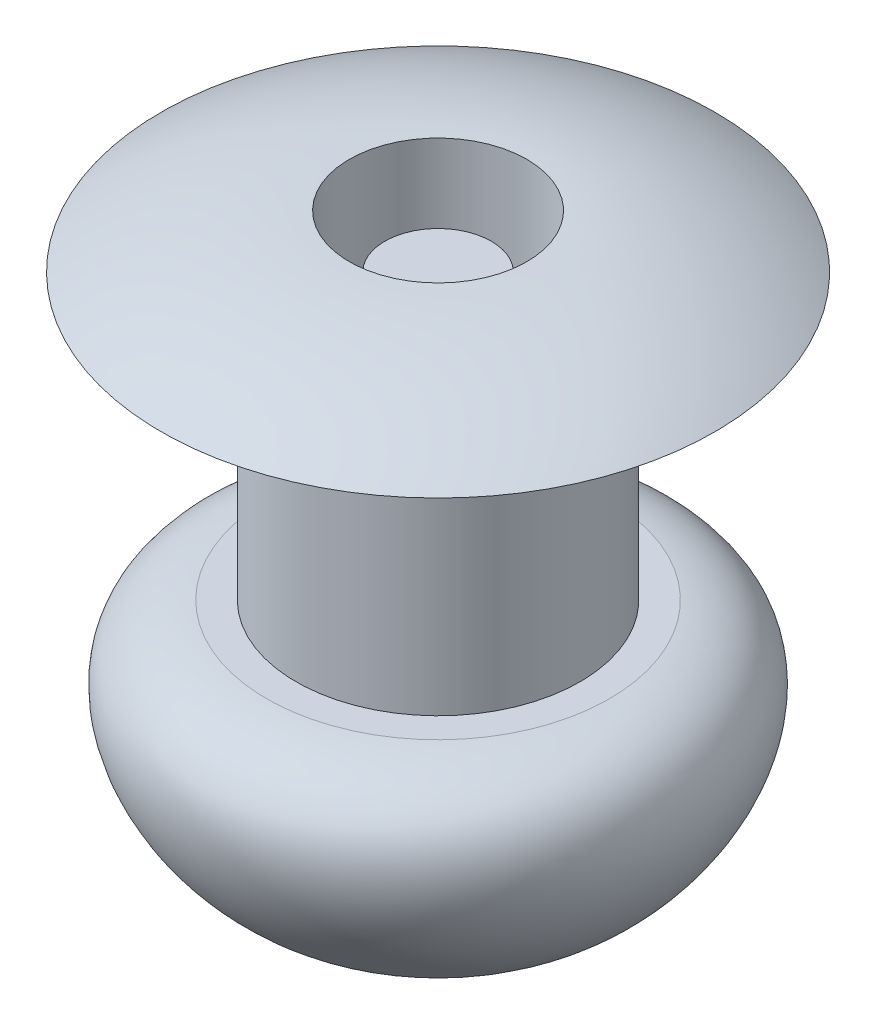
SolidWorks part; units mm, degrees
material "AISI 316 Stal nierdzewna odprężona (SS)"
ref_plane "Płaszczyzna przednia" through (0, 0, 0) normal (0, 0, 1) x (1, 0, 0)
ref_plane "Płaszczyzna górna" through (0, 0, 0) normal (0, 1, 0) x (1, 0, 0)
ref_plane "Płaszczyzna prawa" through (0, 0, 0) normal (1, 0, 0) x (0, 0, -1)
sketch "Szkic1" plane through (0, 0, 0) normal (1, 0, 0) x (0, 0, -1)
  line L0 (0, 0) -> (0, -4)
  line L1 (0, 0) -> (-0.75, 0)
  line L2 (-0.75, 0) -> (-0.75, -4)
  line L3 (-0.75, -4) -> (-1.25, -4)
  line L4 (-1.25, -4) -> (-1.25, 0.75)
  line L5 (-3.9, 0) -> (-2, 0)
  line L6 (-2, 0) -> (-2, -4)
  line L7 (-2, -4) -> (-2.4139, -4)
  line L8 (0, 0) -> (0, 0.4842) construction
  line L10 (0, -4) -> (0, -5.5)
  line L11 (-573, -4) -> (7, -4) construction
  arc A0 (-1.25, 0.75) -> (-3.9, 0) centre (-1.25, -4.3067) ccw
  ellipse E0 centre (0, -4.75) end of major axis (1.75, -4.75) minor radius 0.75 (-0.956, -5.3782) -> (0, -5.5) ccw
  spline S0 degree 3 poles (-2.4139, -4) (-3.8586, -4.1633) (-3.5584, -6.323) (-0.9713, -7.8719) (-0.3411, -5.792) (-0.956, -5.3782) knots 0 0 0 0 0.454219 0.705201 1 1 1 1
  point P25 (-2.2069, -4)
  dimension "D1" = 7.8
  dimension "D2" = 2.5
  dimension "D3" = 4
  dimension "D4" = 0.75
  dimension "D5" = 1.5
  dimension "D6" = 1.5
  dimension "D7" = 3.5
  dimension "D8" = 3.1855
  dimension "D9" = 2.5026
  dimension "D10" = 1.9
  dimension "D11" = 1.3782
  dimension "D12" = 0.5792
  dimension "D13" = 4.8278
  dimension "D14" = 3.3858
  dimension "D15" = 2.8395
  dimension "D16" = 1.25
  dimension "D17" = 0.6409
  dimension "D18" = 0.956
revolve "Obrót1" add sketch "Szkic1" angle 360 about L8
